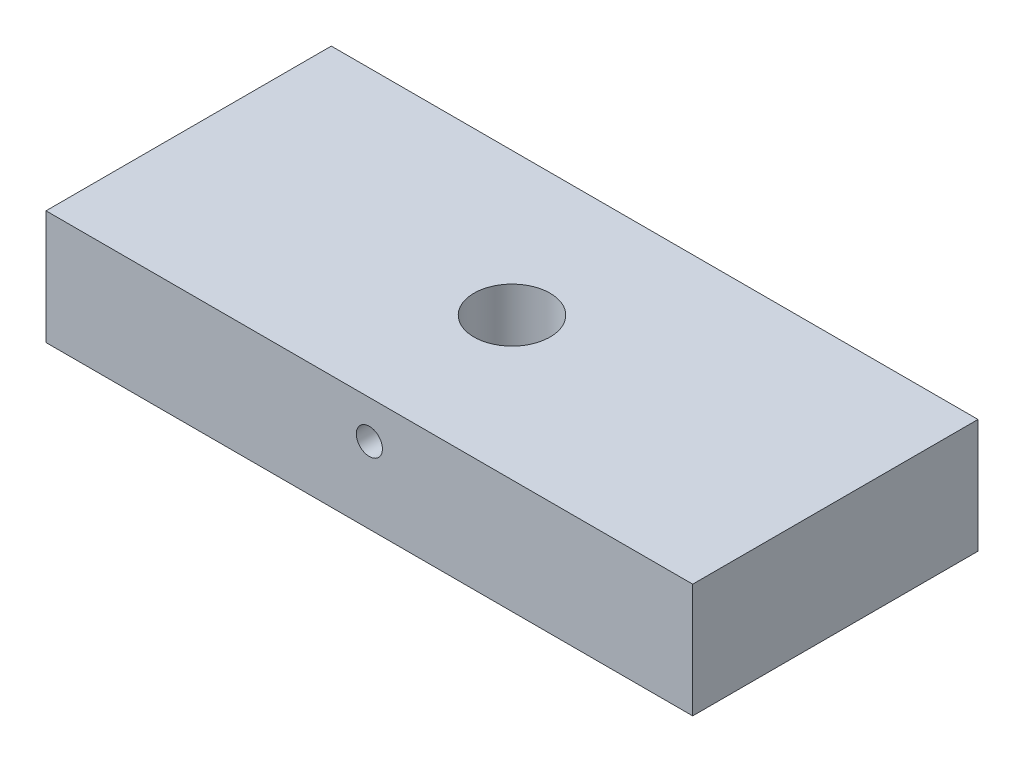
SolidWorks part; units mm, degrees
ref_plane "Front Plane" through (0, 0, 0) normal (0, 0, 1) x (1, 0, 0)
ref_plane "Top Plane" through (0, 0, 0) normal (0, 1, 0) x (1, 0, 0)
ref_plane "Right Plane" through (0, 0, 0) normal (1, 0, 0) x (0, 0, -1)
sketch "Sketch1" plane through (0, 0, 0) normal (0, 1, 0) x (1, 0, 0)
  line L1 (-34, -15) -> (34, -15)
  line L2 (-34, -15) -> (-34, 15)
  line L3 (-34, 15) -> (34, 15)
  line L4 (34, -15) -> (34, 15)
  line L5 (-34, -15) -> (34, 15) construction
  line L6 (-34, 15) -> (34, -15) construction
  point P0 (0, 0)
  dimension "D1" = 30
  dimension "D2" = 68
extrude "Boss-Extrude1" add sketch "Sketch1" along normal blind 12
sketch "Sketch2" plane through (0, 0, 0) normal (0, -1, 0) x (1, 0, 0)
  circle A0 centre (0, 0) radius 11
  dimension "D1" = 22
extrude "Cut-Extrude1" cut sketch "Sketch2" against normal blind 4
sketch "Sketch3" plane through (0, 4, 0) normal (0, -1, 0) x (1, 0, 0)
  circle A0 centre (0, 0) radius 4
  dimension "D1" = 8
extrude "Cut-Extrude2" cut sketch "Sketch3" against normal through all
sketch "Sketch4" plane through (0, 0, 15) normal (0, 0, 1) x (1, 0, 0)
  line L0 (-34, 12) -> (34, 12) construction
  circle A0 centre (0, 8) radius 1.375
  point P2 (0, 0)
  dimension "D1" = 2.75
  dimension "D2" = 4
extrude "Cut-Extrude3" cut sketch "Sketch4" against normal up to next
